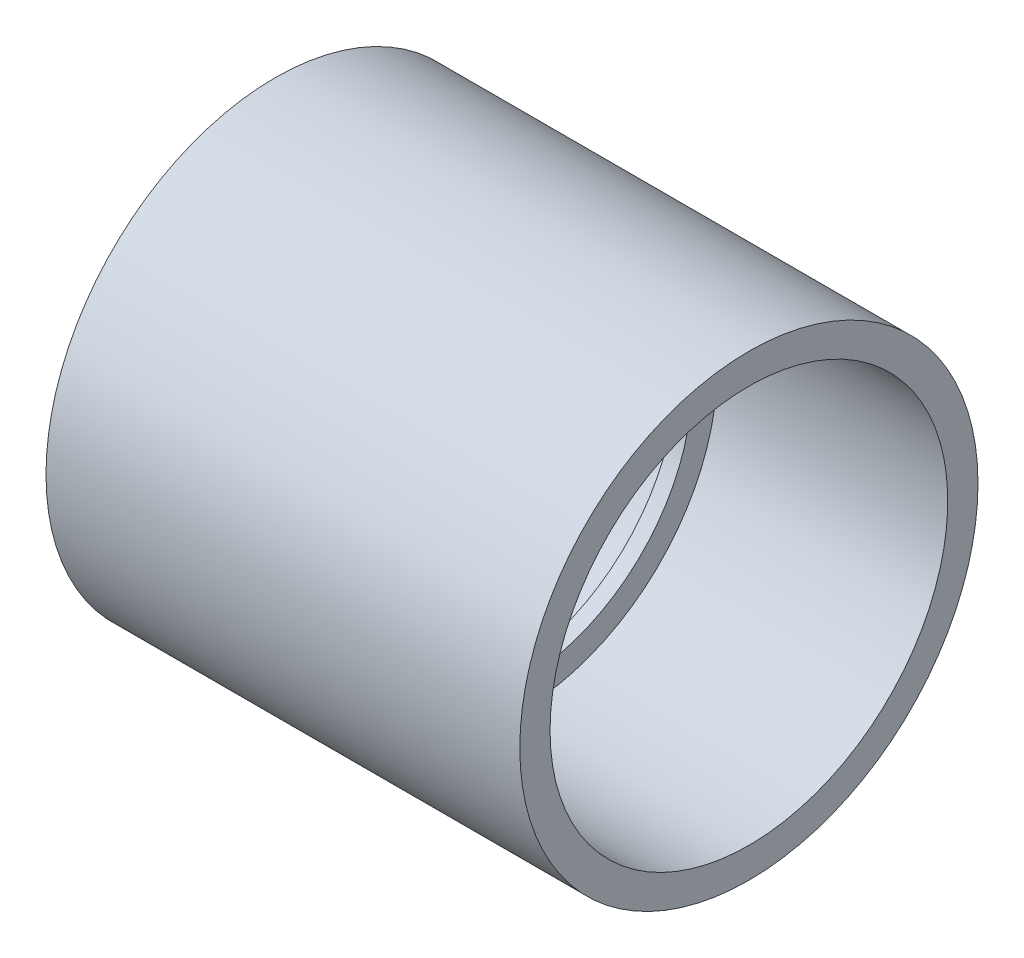
SolidWorks part; units mm, degrees
ref_plane "Front Plane" through (0, 0, 0) normal (0, 0, 1) x (1, 0, 0)
ref_plane "Top Plane" through (0, 0, 0) normal (0, 1, 0) x (1, 0, 0)
ref_plane "Right Plane" through (0, 0, 0) normal (1, 0, 0) x (0, 0, -1)
sketch "Sketch0" plane through (0, 0, 0) normal (0, 0, 1) x (1, 0, 0)
  line L0 (-36.1156, 0) -> (0, 0) construction
  line L2 (-1.1906, 0) -> (0, 0) construction
  line L3 (0, 0) -> (0, 14.4499) construction
  line L4 (-36.1156, 34.925) -> (-36.1156, -34.925) construction
  line L5 (-1.1906, 30.0863) -> (-36.1156, 30.3149) construction
  line L6 (-1.1906, 30.0863) -> (-1.1906, -30.0863) construction
  line L7 (-1.1906, -30.0863) -> (-36.1156, -30.3149) construction
  line L8 (-36.1156, 30.3149) -> (-36.1156, -30.3149) construction
  line L14 (-1.1906, 26.2509) -> (-1.1906, -26.2509) construction
  dimension "M" = 69.85
  dimension "OD A" = 60.6298
  dimension "OD B" = 60.1726
  dimension "ID" = 52.5018
  dimension "L" = 72.2313
  dimension "N" = 2.3813
sketch "Sketch1" plane through (0, 0, 0) normal (0, 0, 1) x (1, 0, 0)
  line L0 (-36.1156, 0) -> (0, 0) construction
  line L1 (-36.1156, 0) -> (0, 0) construction
  line L3 (-36.1156, -34.925) -> (36.1156, -34.925)
  line L4 (-36.1156, -34.925) -> (-36.1156, -30.3149)
  line L5 (-36.1156, -30.3149) -> (-1.1906, -30.0863)
  line L6 (-1.1906, -26.2509) -> (-1.1906, -30.0863)
  line L7 (-1.1906, -26.2509) -> (1.1906, -26.2509)
  line L8 (0, -26.2509) -> (0, -34.925) construction
  line L9 (1.1906, -26.2509) -> (1.1906, -30.0863)
  line L10 (36.1156, -30.3149) -> (1.1906, -30.0863)
  line L11 (36.1156, -34.925) -> (36.1156, -30.3149)
revolve "Revolve1" add sketch "Sketch1" angle 360 about L1
